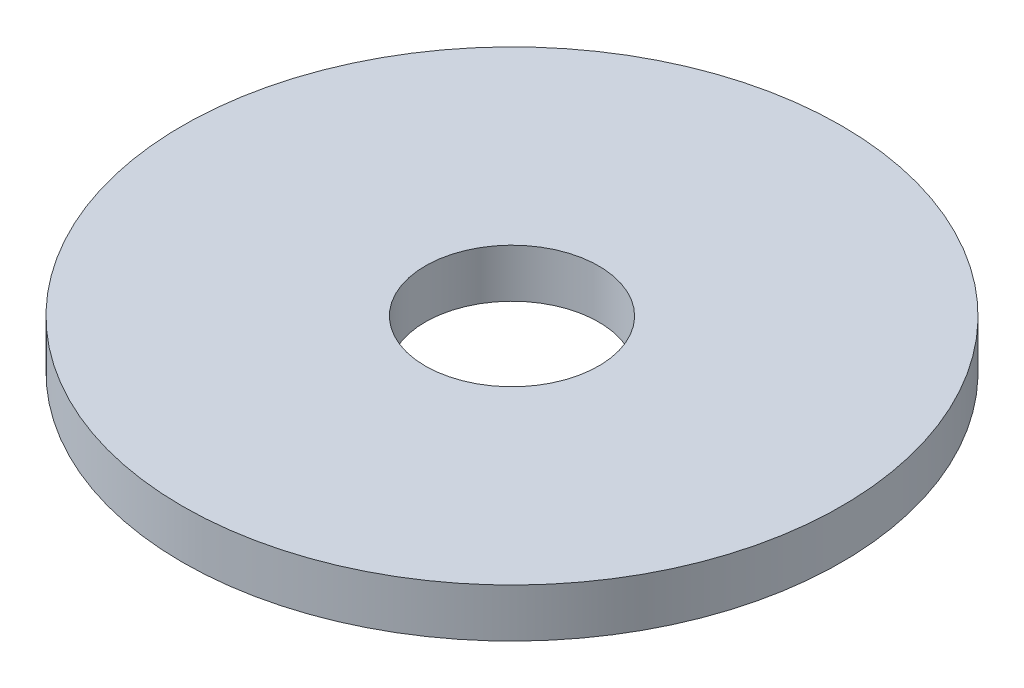
SolidWorks part; units mm, degrees
ref_plane "Front Plane" through (0, 0, 0) normal (0, 0, 1) x (1, 0, 0)
ref_plane "Top Plane" through (0, 0, 0) normal (0, 1, 0) x (1, 0, 0)
ref_plane "Right Plane" through (0, 0, 0) normal (1, 0, 0) x (0, 0, -1)
sketch "Sketch1" plane through (0, 0, 0) normal (0, 1, 0) x (1, 0, 0)
  circle A0 centre (0, 0) radius 95
  dimension "FLANGE_OD" = 190
extrude "Boss-Extrude1" add sketch "Sketch1" along normal blind 14
sketch "Sketch2" plane through (0, 0, 0) normal (0, 1, 0) x (1, 0, 0)
  circle A0 centre (0, 0) radius 25
  dimension "BORE_D" = 50
extrude "Cut-Extrude1" cut sketch "Sketch2" along normal through all
sketch "Sketch3" plane through (0, 14, 0) normal (0, 1, 0) x (1, 0, 0)
  circle A0 centre (0, 0) radius 19.3359 construction
  circle A1 centre (-19.3359, 0) radius 5.0149
  dimension "BOLT_D" = 10.0299
  dimension "BOLT_PCD" = 38.6718
extrude "Cut-Extrude2" cut sketch "Sketch3" against normal blind 11.037 rebuild error yes
pattern_circular "CirPattern1" count 6 over 360 rebuild error yes
